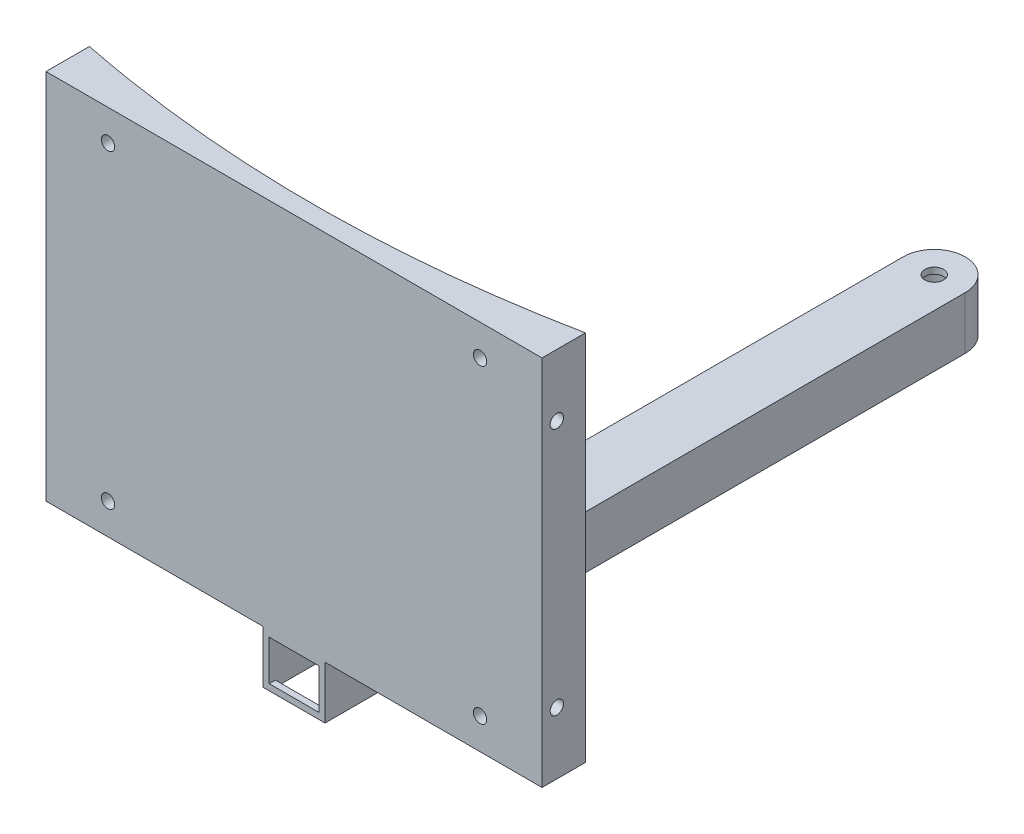
SolidWorks part; units mm, degrees
ref_plane "Front Plane" through (0, 0, 0) normal (0, 0, 1) x (1, 0, 0)
ref_plane "Top Plane" through (0, 0, 0) normal (0, 1, 0) x (1, 0, 0)
ref_plane "Right Plane" through (0, 0, 0) normal (1, 0, 0) x (0, 0, -1)
sketch "Sketch1" plane through (0, 0, 0) normal (0, 1, 0) x (1, 0, 0)
  line L0 (0, -200) -> (0, 0) construction
  line L1 (-225, -136.7187) -> (225, -136.7187) construction
  parabola Q0 (-225, -136.7187) -> (225, -136.7187) focus (0, 0) apex (0, -200) construction
  spline S0 degree 1 poles (-225.2451, -137.1545) (225.2451, -137.1545) knots 0 0 1 1 construction
  spline S1 degree 3 poles (-225.2451, -137.1545) (-222.9082, -138.4691) (-218.2041, -141.0739) (-208.8273, -146.1009) (-197.0951, -152.0818) (-183.0206, -158.7616) (-164.2523, -167.0094) (-140.7912, -176.0823) (-112.6357, -184.9909) (-84.4784, -191.9202) (-46.9336, -198.52) (0, -201.82) (46.9336, -198.52) (84.4784, -191.9202) (112.6357, -184.9909) (140.7912, -176.0823) (164.2523, -167.0094) (183.0206, -158.7616) (197.0951, -152.0818) (208.8273, -146.1009) (218.2041, -141.0739) (222.9082, -138.4691) (225.2451, -137.1545) knots 0.496023 0.496023 0.496023 0.496023 0.496147 0.496271 0.49652 0.496768 0.497017 0.497514 0.498011 0.498508 0.499006 0.5 0.500994 0.501492 0.501989 0.502486 0.502983 0.503232 0.50348 0.503729 0.503853 0.503977 0.503977 0.503977 0.503977 construction
  dimension "D1" = 450
  dimension "D2" = 200
  dimension "D3" = 0.5
sketch "Sketch4" plane through (0, 0, 0) normal (0, 1, 0) x (1, 0, 0)
  line L0 (-80, -157.049) -> (-80, -357.049) construction
  line L1 (80, -173.7313) -> (80, -373.7313) construction
  line L2 (0, -200) -> (0, 0) construction
  line L3 (-80, -192.5099) -> (-80, -206.5)
  line L4 (80, -192.5099) -> (80, -206.5)
  line L5 (-80, -206.5) -> (80, -206.5)
  spline S0 degree 3 poles (1573.6078, -1009.9911) (-454.8299, 36.4001) (-329.3751, -81.4734) (-208.8273, -146.1009) (-197.0951, -152.0818) (-183.0206, -158.7616) (-164.2523, -167.0094) (-140.7912, -176.0823) (-112.6357, -184.9909) (-84.4784, -191.9202) (-46.9336, -198.52) (0, -201.82) (46.9336, -198.52) (84.4784, -191.9202) (112.6357, -184.9909) (140.7912, -176.0823) (164.2523, -167.0094) (183.0206, -158.7616) (197.0951, -152.0818) (208.8273, -146.1009) (329.3765, -81.4727) (454.8329, 36.4029) (-1573.6829, -1010.0298) knots 0.490128 0.490128 0.490128 0.490128 0.496147 0.496271 0.49652 0.496768 0.497017 0.497514 0.498011 0.498508 0.499006 0.5 0.500994 0.501492 0.501989 0.502486 0.502983 0.503232 0.50348 0.503729 0.503853 0.509872 0.509872 0.509872 0.509872 only from (-225.2451, -137.1545) to (225.2451, -137.1545) construction
  spline S1 degree 3 poles (-80, -192.5099) (-72.1067, -194.0866) (-45.4407, -198.6249) (0, -201.82) (45.4407, -198.6249) (72.1067, -194.0866) (80, -192.5099) knots 0.498588 0.498588 0.498588 0.498588 0.499006 0.5 0.500994 0.501412 0.501412 0.501412 0.501412
  point P2 (0, -206.5)
  point P14 (0, -200.5)
  dimension "D2" = 80
  dimension "D3" = 80
  dimension "D1" = 6
extrude "Boss-Extrude3" add sketch "Sketch4" along normal blind 120
sketch "Sketch6" plane through (0, 0, 0) normal (0, -1, 0) x (1, 0, 0)
  line L0 (10, 0) -> (10, 206.5)
  line L1 (-80, 206.5) -> (80, 206.5) construction
  line L2 (10, 206.5) -> (-10, 206.5)
  line L3 (-10, 206.5) -> (-10, 0)
  line L4 (0, 200) -> (0, 0) construction
  arc A0 (10, 0) -> (-10, 0) centre (0, 0) cw
  dimension "D1" = 10
extrude "Boss-Extrude4" add sketch "Sketch6" along normal blind 2
sketch "Sketch7" plane through (0, -2, 0) normal (0, -1, 0) x (1, 0, 0)
  line L0 (8, 0) -> (8, 204.5)
  line L1 (8, 204.5) -> (-8, 204.5)
  line L2 (-8, 204.5) -> (-8, 0)
  line L3 (10, 0) -> (10, 206.5)
  line L4 (10, 206.5) -> (-10, 206.5)
  line L5 (-10, 206.5) -> (-10, 0)
  line L6 (10, 0) -> (10, 206.5)
  line L7 (10, 206.5) -> (-10, 206.5)
  line L8 (-10, 206.5) -> (-10, 0)
  arc A0 (-8, 0) -> (8, 0) centre (0, 0) ccw
  arc A1 (-10, 0) -> (10, 0) centre (0, 0) ccw
  arc A2 (-10, 0) -> (10, 0) centre (0, 0) ccw
  dimension "D1" = 0
  dimension "D2" = 2
extrude "Boss-Extrude5" add sketch "Sketch7" along normal blind 15
sketch "Sketch8" plane through (0, 0, 206.5) normal (0, 0, 1) x (1, 0, 0)
  line L0 (8, -15) -> (-8, -15)
  line L1 (10, -17) -> (-10, -17) construction
  line L2 (10, -17) -> (10, 0) construction
  line L3 (10, 0) -> (-10, 0) construction
  line L4 (-10, -17) -> (-10, 0) construction
  line L5 (-8, -15) -> (-8, -2)
  line L6 (8, -2) -> (-8, -2)
  line L7 (8, -15) -> (8, -2)
  dimension "D1" = 2
extrude "Cut-Extrude2" cut sketch "Sketch8" against normal blind 15
sketch "Sketch10" plane through (80, 0, 0) normal (1, 0, 0) x (0, 0, -1)
  circle A0 centre (-201.7286, 100) radius 2.15
  circle A1 centre (-201.7286, 20) radius 2.15
  dimension "D1" = 4.3
extrude "Cut-Extrude3" cut sketch "Sketch10" against normal blind 10
mirror "Mirror1" about plane through (0, 0, 0) normal (1, 0, 0) of "Cut-Extrude3"
sketch "Sketch11" plane through (0, 0, 206.5) normal (0, 0, 1) x (1, 0, 0)
  circle A0 centre (60, 110) radius 2.15
  circle A1 centre (60, 10) radius 2.15
  circle A2 centre (-60, 110) radius 2.15
  circle A3 centre (-60, 10) radius 2.15
  dimension "D1" = 4.3
extrude "Cut-Extrude4" cut sketch "Sketch11" against normal blind 7
sketch "Sketch12" plane through (0, 0, 0) normal (0, 1, 0) x (1, 0, 0)
  circle A0 centre (0, 0) radius 3
  dimension "D1" = 6
extrude "Cut-Extrude5" cut sketch "Sketch12" against normal blind 7
sketch "Sketch14" plane through (0, 0, 206.5) normal (0, 0, 1) x (1, 0, 0)
  line L0 (10, 0) -> (10, -17) construction
  line L1 (10, -6.6126) -> (10, -9.2583)
  circle A0 centre (11.5, -7.9355) radius 1.5
  arc A1 (10, -9.2583) -> (10, -6.6126) centre (11.5, -7.9355) ccw
  dimension "D1" = 3
  dimension "D2" = 4
equation "\"Focus\"= 200mm"
equation "\"Dish Width\"= 450mm"
equation "\"Plate Thickness\"= 0.5mm"
equation "\"D1@Sketch1\"=\"Dish Width\""
equation "\"D2@Sketch1\"=\"Focus\""
equation "\"D3@Sketch1\"=\"Plate Thickness\""
equation "\"D3@Sketch4\"=\"D2@Sketch4\""
